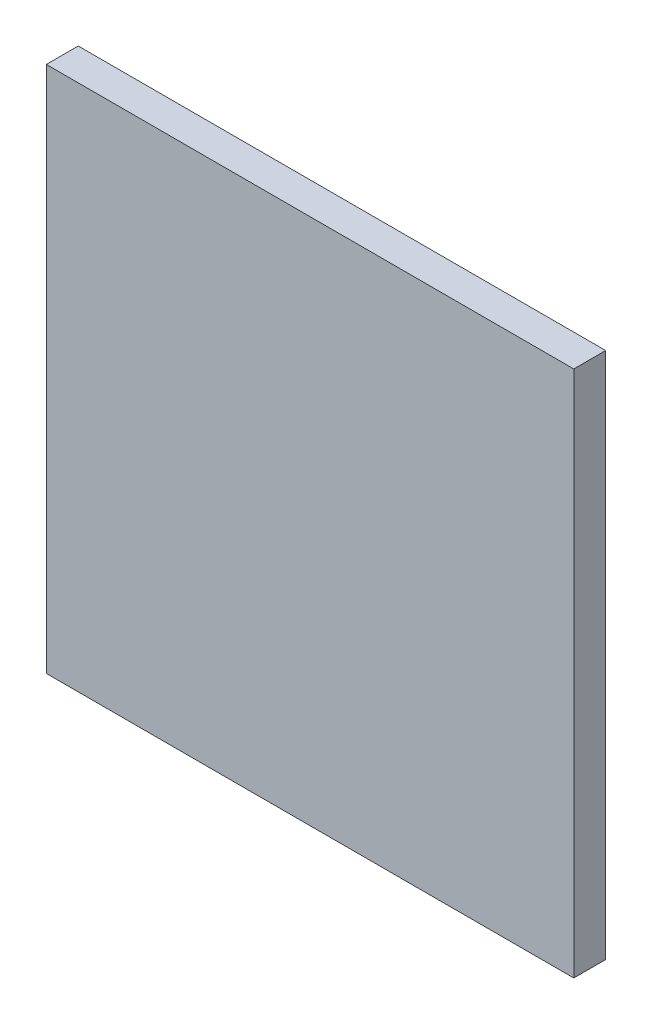
SolidWorks part; units mm, degrees
ref_plane "Front Plane" through (0, 0, 0) normal (0, 0, 1) x (1, 0, 0)
ref_plane "Top Plane" through (0, 0, 0) normal (0, 1, 0) x (1, 0, 0)
ref_plane "Right Plane" through (0, 0, 0) normal (1, 0, 0) x (0, 0, -1)
sketch "Sketch1" plane through (0, 0, 0) normal (0, 0, 1) x (1, 0, 0)
  line L1 (-3.15, -3.15) -> (3.15, -3.15)
  line L2 (-3.15, -3.15) -> (-3.15, 3.15)
  line L3 (-3.15, 3.15) -> (3.15, 3.15)
  line L4 (3.15, -3.15) -> (3.15, 3.15)
  line L5 (-3.15, -3.15) -> (3.15, 3.15) construction
  line L6 (-3.15, 3.15) -> (3.15, -3.15) construction
  point P0 (0, 0)
  dimension "D1" = 6.3
  dimension "D2" = 6.3
extrude "chip" add sketch "Sketch1" along normal blind 0.381
equation "\"pcb_length\"= 25.0 ' length of the chip in the direction of the feadline"
equation "\"pcb_side\"= 10    ' length of the chip in the other direction"
equation "\"pcb_width\"= 0.381 ' thickness of the PCB (381 um)"
equation "\"wall_width\"= 1  ' minimal width from the box walls"
equation "\"route_width\"= 0.5 ' The width of the trace on the lid for not touching the signal roates."
equation "\"route_clearence\"= 0.04 ' The clearence depth of the trace on the lid for not touching the signal roates."
equation "\"route_chip_clearence\"= 1"
equation "\"port_count\"= 2"
equation "\"port_space\"= 1.5"
equation "\"port_length\"= 5.1"
equation "\"port_width\"= 5.1"
equation "\"chip_length\"= 6.3 ' length of the chip in the direction of the feadline"
equation "\"chip_side\"= 6.3 ' length of the chip in the other direction"
equation "\"chip_width\"= 0.381 ' thickness of the chip (381 um)"
equation "\"pedestal_depth\"= 0.0 ' depth of the pedestal under the chip"
equation "\"chip_leg\"= 0.8  ' size of the legs the chip lay on in case there is pedestal"
equation "\"wing_length\"= 10 ' Mounting wing size"
equation "\"wing_width\"= 1 ' mounting wing width"
equation "\"bonding_clearence\"= 0.0"
equation "\"box_height\"= \"wall_width\" + \"pedestal_depth\" + \"pcb_width\""
equation "\"box_length\"= \"pcb_length\" + 2 * \"wall_width\""
equation "\"box_side\"= \"pcb_side\" + 2 * \"wall_width\""
equation "\"D1@Sketch1\"=\"chip_length\""
equation "\"D2@Sketch1\"=\"chip_side\""
equation "\"D1@chip\" = \"chip_width\""
